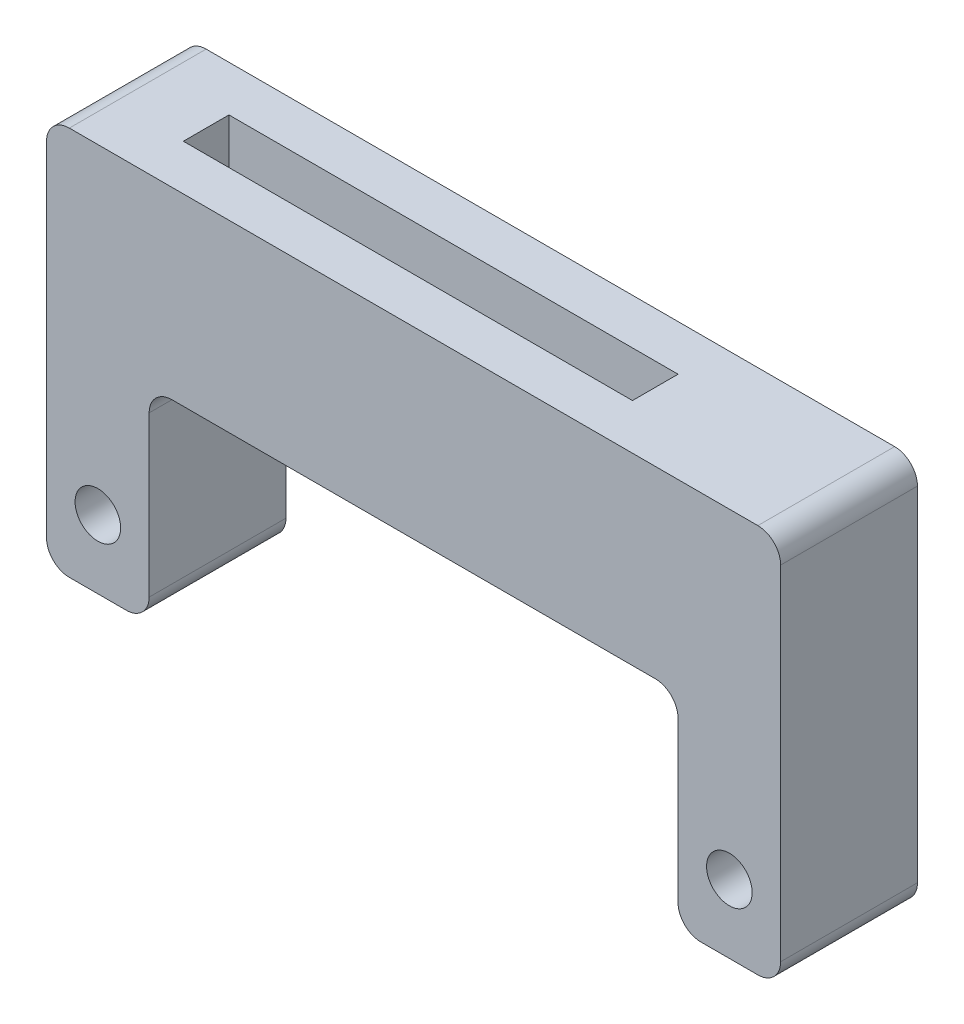
SolidWorks part; units mm, degrees
ref_plane "Front Plane" through (0, 0, 0) normal (0, 0, 1) x (1, 0, 0)
ref_plane "Top Plane" through (0, 0, 0) normal (0, 1, 0) x (1, 0, 0)
ref_plane "Right Plane" through (0, 0, 0) normal (1, 0, 0) x (0, 0, -1)
sketch "Sketch2" plane through (0, 0, 0) normal (0, 0, 1) x (1, 0, 0)
  line L1 (-16.1, -8.534) -> (16.1, -8.534)
  line L2 (-16.1, -8.534) -> (-16.1, 8.534)
  line L3 (-16.1, 8.534) -> (16.1, 8.534)
  line L4 (16.1, -8.534) -> (16.1, 8.534)
  line L5 (-16.1, -8.534) -> (16.1, 8.534) construction
  line L6 (-16.1, 8.534) -> (16.1, -8.534) construction
  point P0 (0, 0)
  dimension "D1" = 17.068
  dimension "D2" = 32.2
extrude "Boss-Extrude1" add sketch "Sketch2" along normal mid plane 6
sketch "Sketch3" plane through (0, 8.534, 0) normal (0, 1, 0) x (1, 0, 0)
  line L0 (-16.1, -3) -> (-16.1, 3) construction
  line L1 (-12.1, 1) -> (7.6, 1)
  line L2 (-12.1, 1) -> (-12.1, -1)
  line L3 (-12.1, -1) -> (7.6, -1)
  line L4 (7.6, 1) -> (7.6, -1)
  line L5 (16.1, -3) -> (16.1, 3) construction
  line L6 (16.1, 3) -> (-16.1, 3) construction
  dimension "D1" = 2
  dimension "D2" = 4
  dimension "D3" = 8.5
  dimension "D4" = 2
extrude "Cut-Extrude1" cut sketch "Sketch3" against normal blind 2.5
sketch "Sketch4" plane through (0, 0, 3) normal (0, 0, 1) x (1, 0, 0)
  line L0 (-16.1, -8.534) -> (16.1, -8.534) construction
  line L1 (-11.6, -8.534) -> (11.6, -8.534)
  line L2 (-11.6, -8.534) -> (-11.6, 0.466)
  line L3 (-11.6, 0.466) -> (11.6, 0.466)
  line L4 (11.6, -8.534) -> (11.6, 0.466)
  line L5 (-16.1, 8.534) -> (-16.1, -8.534) construction
  line L6 (16.1, -8.534) -> (16.1, 8.534) construction
  dimension "D1" = 9
  dimension "D2" = 4.5
  dimension "D3" = 4.5
extrude "Cut-Extrude2" cut sketch "Sketch4" against normal through all
sketch "Sketch5" plane through (0, 0, 3) normal (0, 0, 1) x (1, 0, 0)
  line L0 (-16.1, 8.534) -> (-16.1, -8.534) construction
  line L1 (16.1, -8.534) -> (16.1, 8.534) construction
  line L2 (-16.1, -8.534) -> (-11.6, -8.534) construction
  circle A0 centre (-13.85, -5.534) radius 1
  circle A2 centre (13.85, -5.534) radius 1
  dimension "D1" = 2
  dimension "D2" = 2.25
  dimension "D3" = 2.25
  dimension "D4" = 3
extrude "Cut-Extrude3" cut sketch "Sketch5" against normal through all
fillet "Fillet1" radius 1 8 edges at (16.1, 8.534, 0) (16.1, -8.534, 0) (11.6, -8.534, 0) (11.6, 0.466, 0) (-11.6, 0.466, 0) (-11.6, -8.534, 0) (-16.1, -8.534, 0) (-16.1, 8.534, 0)
